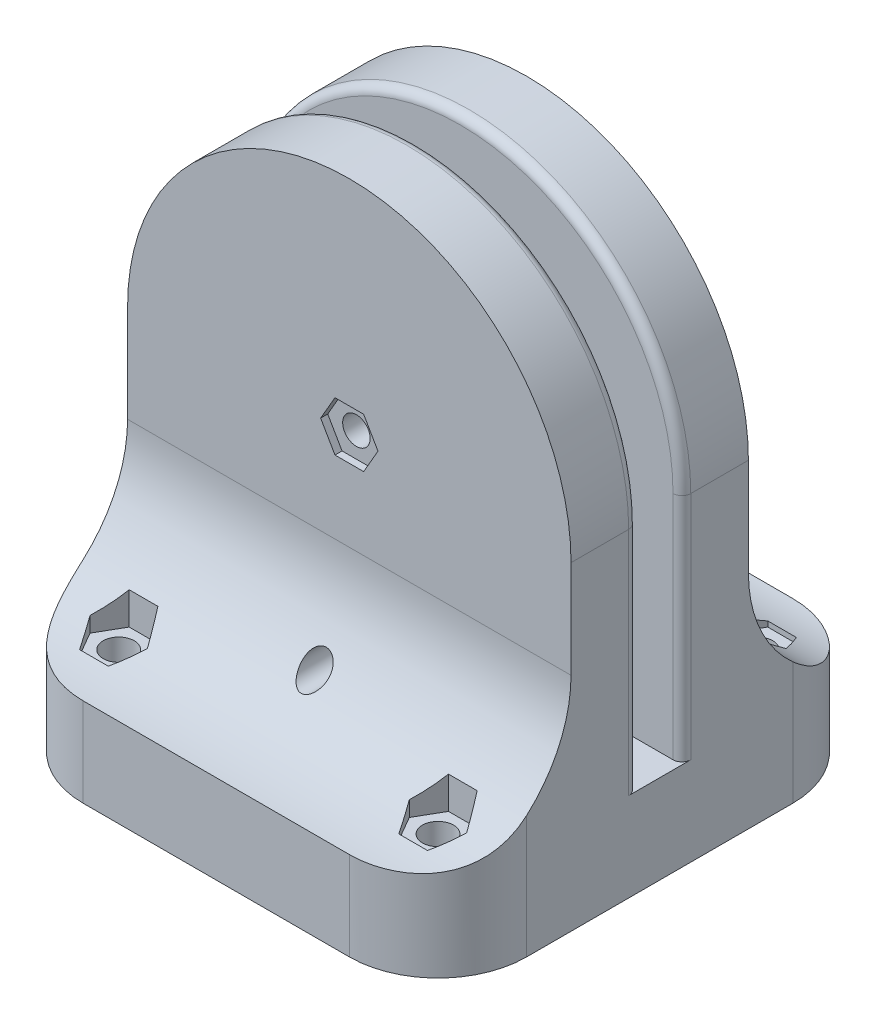
SolidWorks part; units mm, degrees
ref_plane "正面" through (0, 0, 0) normal (0, 0, 1) x (1, 0, 0)
ref_plane "平面" through (0, 0, 0) normal (0, 1, 0) x (1, 0, 0)
ref_plane "右側面" through (0, 0, 0) normal (1, 0, 0) x (0, 0, -1)
sketch "ｽｹｯﾁ1" plane through (0, 0, 0) normal (0, 1, 0) x (1, 0, 0)
  line L1 (25, 25) -> (-25, 25)
  line L2 (25, 25) -> (25, -25)
  line L3 (25, -25) -> (-25, -25)
  line L4 (-25, 25) -> (-25, -25)
  line L5 (25, 25) -> (-25, -25) construction
  line L6 (25, -25) -> (-25, 25) construction
  point P0 (0, 0)
  dimension "D1" = 50
  dimension "D2" = 50
extrude "ﾎﾞｽ - 押し出し1" add sketch "ｽｹｯﾁ1" along normal blind 10
sketch "ｽｹｯﾁ2" plane through (0, 0, 0) normal (0, 0, 1) x (1, 0, 0)
  line L0 (25, 10) -> (-25, 10)
  line L1 (-25, 10) -> (25, 10)
  line L4 (-25, 36) -> (-25, 10)
  line L5 (-25, 10) -> (25, 10)
  line L6 (-12, 10) -> (6.5, 10)
  line L7 (-25, 10) -> (25, 10)
  line L8 (25, 36) -> (25, 10)
  arc A1 (25, 36) -> (-25, 36) centre (0, 36) ccw
  circle A2 centre (0, 36) radius 1.55
  dimension "D1" = 26
  dimension "D3" = 0
  dimension "D2" = 25
  dimension "3.1" = 3.1
  dimension "D4" = 26
  dimension "D5" = 26
sketch "ｽｹｯﾁ6" plane through (0, 0, 0) normal (0, 1, 0) x (1, 0, 0)
  line L0 (0, -25) -> (0, 25) construction
  line L1 (-25, -25) -> (25, -25) construction
  line L2 (25, 25) -> (-25, 25) construction
  line L3 (-25, 0) -> (25, 0) construction
  line L4 (-25, 25) -> (-25, -25) construction
  line L5 (25, -25) -> (25, 25) construction
  circle A0 centre (-18, -18) radius 1.75
  circle A1 centre (18, -18) radius 1.75
  circle A2 centre (18, 18) radius 1.75
  circle A3 centre (-18, 18) radius 1.75
  dimension "D1" = 3.5
  dimension "D2" = 18
  dimension "D3" = 18
extrude "ｶｯﾄ - 押し出し3" cut sketch "ｽｹｯﾁ6" against normal blind 5 and the other way through all
fillet "ﾌｨﾚｯﾄ1" radius 10 4 edges at (-25, 5, 25) (-25, 5, -25) (25, 5, -25) (25, 5, 25)
extrude "ﾎﾞｽ - 押し出し5" add sketch "ｽｹｯﾁ2" along normal blind 7.5 from offset 2.5 contours L8 A1 L4 L0 L5 A2 region at (0, 33.1492, 0)
extrude "ﾎﾞｽ - 押し出し6" add sketch "ｽｹｯﾁ2<12>" against normal blind 7.5 from offset 2.5 contours L8 A1 L4 L0 L5 A2 region at (0, 33.1492, 0) offset against normal yes
sketch "ｽｹｯﾁ2<12>" plane through (0, 0, 0) normal (0, 0, 1) x (1, 0, 0) same geometry as "ｽｹｯﾁ2"
sketch "ｽｹｯﾁ13" plane through (0, 0, 0) normal (0, 0, 1) x (1, 0, 0)
  circle A0 centre (0, 36) radius 21
  circle A1 centre (0, 15) radius 1.55
  point P10 (0, 36)
  dimension "D1" = 42
  dimension "3.1" = 3.1
extrude "ｶｯﾄ - 押し出し4" cut sketch "ｽｹｯﾁ13" against normal through all both and the other way through all contours A1
sketch "ｽｹｯﾁ14" plane through (0, 10, 0) normal (0, 1, 0) x (1, 0, 0)
  line L0 (0, 25) -> (0, -25) construction
  line L1 (15, 25) -> (-15, 25) construction
  line L2 (-15, -25) -> (15, -25) construction
  line L3 (-25, 0) -> (25, 0) construction
  line L4 (-25, 2.5) -> (-25, -2.5) construction
  line L5 (25, -2.5) -> (25, 2.5) construction
  line L6 (-19.6166, 15.2) -> (-21.2332, 18)
  line L7 (21.2332, 18) -> (19.6166, 20.8)
  line L8 (19.6166, 20.8) -> (16.3834, 20.8)
  line L9 (16.3834, 20.8) -> (14.7668, 18)
  line L10 (14.7668, 18) -> (16.3834, 15.2)
  line L11 (16.3834, 15.2) -> (19.6166, 15.2)
  line L12 (19.6166, 15.2) -> (21.2332, 18)
  line L13 (-16.3834, 15.2) -> (-19.6166, 15.2)
  line L14 (-14.7668, 18) -> (-16.3834, 15.2)
  line L15 (-16.3834, 20.8) -> (-14.7668, 18)
  line L16 (-19.6166, 20.8) -> (-16.3834, 20.8)
  line L17 (-21.2332, 18) -> (-19.6166, 20.8)
  line L18 (16.3834, -15.2) -> (19.6166, -15.2)
  line L19 (14.7668, -18) -> (16.3834, -15.2)
  line L20 (16.3834, -20.8) -> (14.7668, -18)
  line L21 (19.6166, -20.8) -> (16.3834, -20.8)
  line L22 (21.2332, -18) -> (19.6166, -20.8)
  line L23 (-21.2332, -18) -> (-19.6166, -20.8)
  line L24 (-19.6166, -20.8) -> (-16.3834, -20.8)
  line L25 (-16.3834, -20.8) -> (-14.7668, -18)
  line L26 (-14.7668, -18) -> (-16.3834, -15.2)
  line L27 (-16.3834, -15.2) -> (-19.6166, -15.2)
  line L28 (19.6166, -15.2) -> (21.2332, -18)
  line L29 (-19.6166, -15.2) -> (-21.2332, -18)
  circle A0 centre (18, 18) radius 2.8 construction
  circle A1 centre (-18, 18) radius 2.8 construction
  circle A2 centre (18, -18) radius 2.8 construction
  circle A3 centre (-18, -18) radius 2.8 construction
  dimension "5.6" = 5.6
fillet "ﾌｨﾚｯﾄ3" radius 15 2 edges at (0, 10, -10)
sketch "ｽｹｯﾁ15" plane through (0, 0, 0) normal (0, 0, 1) x (1, 0, 0)
  circle A0 centre (0, 15) radius 3.2
  dimension "D1" = 6.4
sketch "ｽｹｯﾁ16" plane through (0, 0, 0) normal (0, 0, 1) x (1, 0, 0)
  line L1 (-3.2332, 36) -> (-1.6166, 33.2)
  line L2 (-1.6166, 33.2) -> (1.6166, 33.2)
  line L3 (1.6166, 33.2) -> (3.2332, 36)
  line L4 (3.2332, 36) -> (1.6166, 38.8)
  line L5 (1.6166, 38.8) -> (-1.6166, 38.8)
  line L6 (-1.6166, 38.8) -> (-3.2332, 36)
  circle A0 centre (0, 36) radius 2.8 construction
  dimension "5.6" = 5.6
extrude "ｶｯﾄ - 押し出し9" cut sketch "ｽｹｯﾁ16" against normal blind 3.3 from offset 12.5
fillet "ﾌｨﾚｯﾄ5" radius 1 6 edges at (25, 23, -2.5) (-25, 23, -2.5) (0, 61, -2.5) (0, 61, 2.5)
extrude "ｶｯﾄ - 押し出し11" cut sketch "ｽｹｯﾁ14" along normal through all
